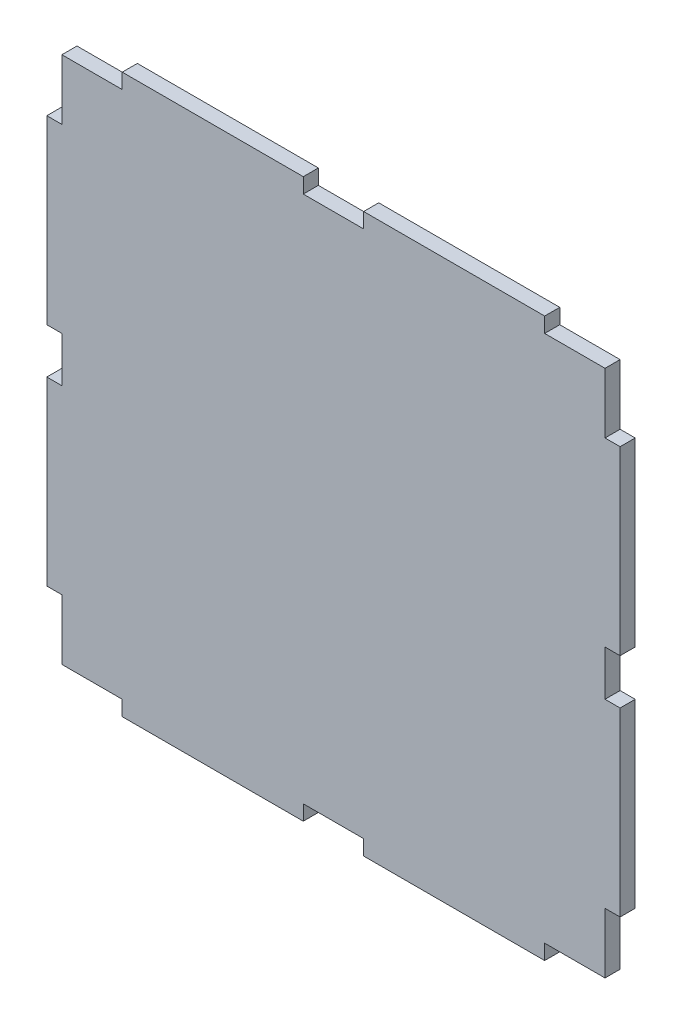
SolidWorks part; units mm, degrees
ref_plane "Front Plane" through (0, 0, 0) normal (0, 0, 1) x (1, 0, 0)
ref_plane "Top Plane" through (0, 0, 0) normal (0, 1, 0) x (1, 0, 0)
ref_plane "Right Plane" through (0, 0, 0) normal (1, 0, 0) x (0, 0, -1)
sketch "Sketch5" plane through (0, 0, 0) normal (0, 0, 1) x (1, 0, 0)
  line L0 (259.6128, -169.2784) -> (259.6128, -391.5284) construction
  line L1 (145.3128, -169.2784) -> (373.9128, -169.2784)
  line L2 (145.3128, -169.2784) -> (145.3128, -391.5284)
  line L3 (145.3128, -391.5284) -> (373.9128, -391.5284)
  line L4 (373.9128, -169.2784) -> (373.9128, -391.5284)
  line L5 (170.7128, -169.2784) -> (246.9128, -169.2784)
  line L6 (170.7128, -169.2784) -> (170.7128, -162.9284)
  line L7 (170.7128, -162.9284) -> (246.9128, -162.9284)
  line L8 (246.9128, -169.2784) -> (246.9128, -162.9284)
  line L9 (138.9628, -194.6784) -> (145.3128, -194.6784)
  line L10 (138.9628, -194.6784) -> (138.9628, -270.8784)
  line L11 (138.9628, -270.8784) -> (145.3128, -270.8784)
  line L12 (145.3128, -194.6784) -> (145.3128, -270.8784)
  line L13 (145.3128, -280.4034) -> (373.9128, -280.4034) construction
  line L14 (272.3128, -169.2784) -> (272.3128, -162.9284)
  line L15 (348.5128, -162.9284) -> (272.3128, -162.9284)
  line L16 (348.5128, -169.2784) -> (348.5128, -162.9284)
  line L17 (348.5128, -391.5284) -> (348.5128, -397.8784)
  line L18 (348.5128, -397.8784) -> (272.3128, -397.8784)
  line L19 (272.3128, -391.5284) -> (272.3128, -397.8784)
  line L20 (246.9128, -391.5284) -> (246.9128, -397.8784)
  line L21 (170.7128, -397.8784) -> (246.9128, -397.8784)
  line L22 (170.7128, -391.5284) -> (170.7128, -397.8784)
  line L23 (138.9628, -289.9284) -> (145.3128, -289.9284)
  line L24 (138.9628, -366.1284) -> (138.9628, -289.9284)
  line L25 (138.9628, -366.1284) -> (145.3128, -366.1284)
  line L26 (380.2628, -366.1284) -> (373.9128, -366.1284)
  line L27 (380.2628, -366.1284) -> (380.2628, -289.9284)
  line L28 (380.2628, -289.9284) -> (373.9128, -289.9284)
  line L29 (380.2628, -270.8784) -> (373.9128, -270.8784)
  line L30 (380.2628, -194.6784) -> (380.2628, -270.8784)
  line L31 (380.2628, -194.6784) -> (373.9128, -194.6784)
  dimension "D1" = 222.25
  dimension "D2" = 228.6
  dimension "D3" = 76.2
  dimension "D4" = 6.35
  dimension "D5" = 25.4
  dimension "D6" = 25.4
extrude "Boss-Extrude1" add sketch "Sketch5" along normal blind 6.35 contours L24 L25 L2 L23 | L3 L22 L21 L20 | L3 L19 L18 L17 | L27 L28 L4 L26 | L1 L16 L15 L14 | L30 L31 L4 L29 | L1 L8 L7 L6 | L10 L11 L2 L9 | L2 L3 L4 L1 region at (208.8128, -166.1034, 0) region at (142.1378, -232.7784, 0) region at (310.4128, -166.1034, 0) region at (142.1378, -328.0284, 0) region at (377.0878, -232.7784, 0) region at (208.8128, -394.7034, 0) region at (377.0878, -328.0284, 0) region at (310.4128, -394.7034, 0)
equation "\"width\"= 9in"
equation "\"Height\"= 18in"
equation "\"thick\"= 0.25"
equation "\"D1@Sketch5\"= \"width\" - \"thick\""
equation "\"D2@Sketch5\" = \"width\""
equation "\"D4@Sketch5\"=\"thick\""
equation "\"D1@Boss-Extrude1\"=\"thick\""
